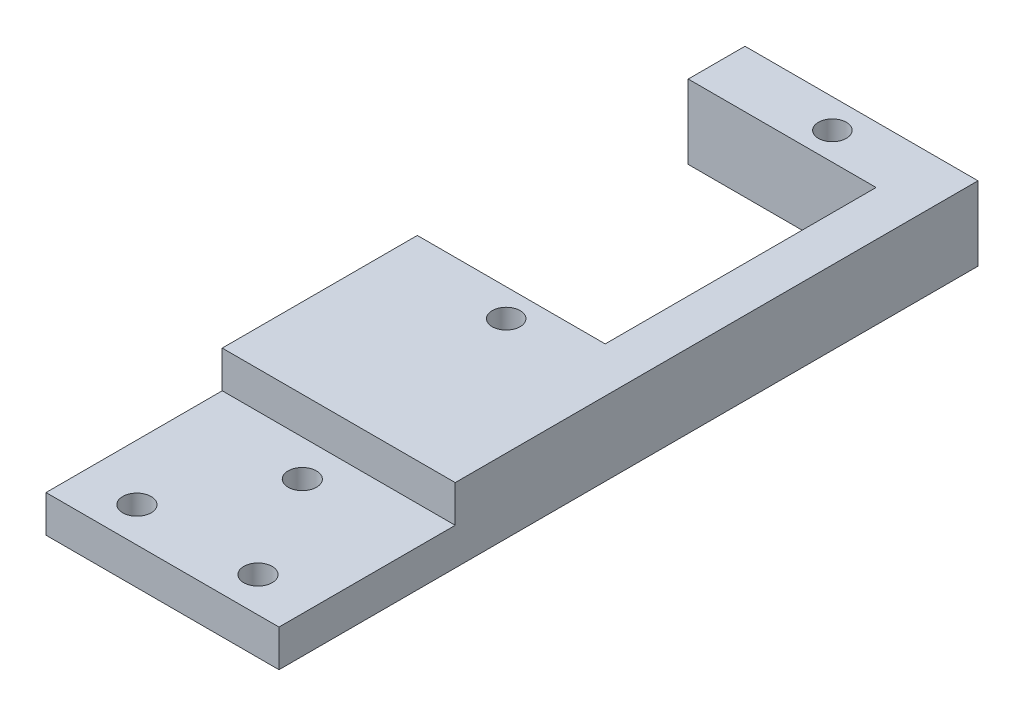
SolidWorks part; units mm, degrees
material "ABS"
ref_plane "Front" through (0, 0, 0) normal (0, 0, 1) x (1, 0, 0)
ref_plane "Top" through (0, 0, 0) normal (0, 1, 0) x (1, 0, 0)
ref_plane "Right" through (0, 0, 0) normal (1, 0, 0) x (0, 0, -1)
sketch "Sketch2" plane through (0, 0, 0) normal (0, 1, 0) x (1, 0, 0)
  line L1 (0, 0) -> (20, 0)
  line L2 (0, 0) -> (0, -60)
  line L3 (0, -60) -> (20, -60)
  line L4 (20, 0) -> (20, -60)
  dimension "D1" = 20
  dimension "D2" = 60
extrude "Boss-Extrude1" add sketch "Sketch2" along normal blind 6.35
sketch "Sketch4" plane through (0, 6.35, 0) normal (0, 1, 0) x (1, 0, 0)
  line L0 (0, 0) -> (0, -60) construction
  line L1 (0, -4.873) -> (16.127, -4.873)
  line L2 (0, -4.873) -> (0, -28.127)
  line L3 (0, -28.127) -> (16.127, -28.127)
  line L4 (16.127, -4.873) -> (16.127, -28.127)
  line L5 (20, -60) -> (20, 0) construction
  line L6 (20, 0) -> (0, 0) construction
  dimension "D1" = 3.873
  dimension "D2" = 4.873
  dimension "D3" = 23.254
extrude "Cut-Extrude1" cut sketch "Sketch4" against normal through all
hole_wizard "M2 Clearance Hole1" positions "Sketch8" profile "Sketch9" hole size "M2" standard "IS" end condition through all
sketch "Sketch8" plane through (0, 6.35, 0) normal (0, 1, 0) x (1, 0, 0)
  line L0 (10, 0) -> (10, -60) construction
  line L1 (20, 0) -> (0, 0) construction
  line L2 (0, -60) -> (20, -60) construction
  line L3 (0, -28.127) -> (16.127, -28.127) construction
  point P9 (10, -2.5)
  point P11 (10, -30.5)
  dimension "D1" = 2.373
  dimension "D2" = 2.5
sketch "Sketch9" plane through (10, 6.35, 30.5) normal (1, 0, 0) x (0, 0, 1)
  line L0 (0, 0) -> (0, 6.35)
  line L1 (0, 6.35) -> (1.2, 6.35)
  line L2 (1.2, 6.35) -> (1.2, 0)
  line L5 (1.2, 0) -> (0, 0)
  line L11 (0, -6.35) -> (0, 107.95) construction
  dimension "Thru Hole Dia." = 2.4
  dimension "Thru Hole Depth" = 6.35
sketch "Sketch10" plane through (20, 0, 0) normal (1, 0, 0) x (0, 0, -1)
  line L0 (-60, 6.35) -> (-60, 0) construction
  line L1 (-60, 6.35) -> (-44.873, 6.35)
  line L2 (-60, 6.35) -> (-60, 3.175)
  line L3 (-60, 3.175) -> (-44.873, 3.175)
  line L4 (-44.873, 6.35) -> (-44.873, 3.175)
  dimension "D1" = 15.127
extrude "Cut-Extrude2" cut sketch "Sketch10" against normal through all
sketch "Sketch12" plane through (0, 3.175, 0) normal (0, 1, 0) x (1, 0, 0)
  line L0 (10, -60) -> (10, -44.873) construction
  line L1 (0, -60) -> (20, -60) construction
  line L2 (0, -44.873) -> (20, -44.873) construction
  line L3 (10, -48) -> (15.1962, -57) construction
  line L4 (15.1962, -57) -> (4.8038, -57) construction
  line L5 (4.8038, -57) -> (10, -48) construction
  dimension "D1" = 9
  dimension "D2" = 3
hole_wizard "#2 Clearance Hole1" positions "Sketch13" profile "Sketch14" hole size "#2" standard "ANSI Inch" end condition through all
sketch "Sketch13" plane through (0, 3.175, 0) normal (0, 1, 0) x (1, 0, 0)
  point P0 (10, -48)
  point P3 (4.8038, -57)
  point P6 (15.1962, -57)
sketch "Sketch14" plane through (10, 3.175, 48) normal (1, 0, 0) x (0, 0, 1)
  line L0 (0, 0) -> (0, 3.175)
  line L1 (0, 3.175) -> (1.2192, 3.175)
  line L2 (1.2192, 3.175) -> (1.2192, 0)
  line L5 (1.2192, 0) -> (0, 0)
  line L11 (0, -6.35) -> (0, 107.95) construction
  dimension "Thru Hole Dia." = 2.4384
  dimension "Thru Hole Depth" = 3.175
